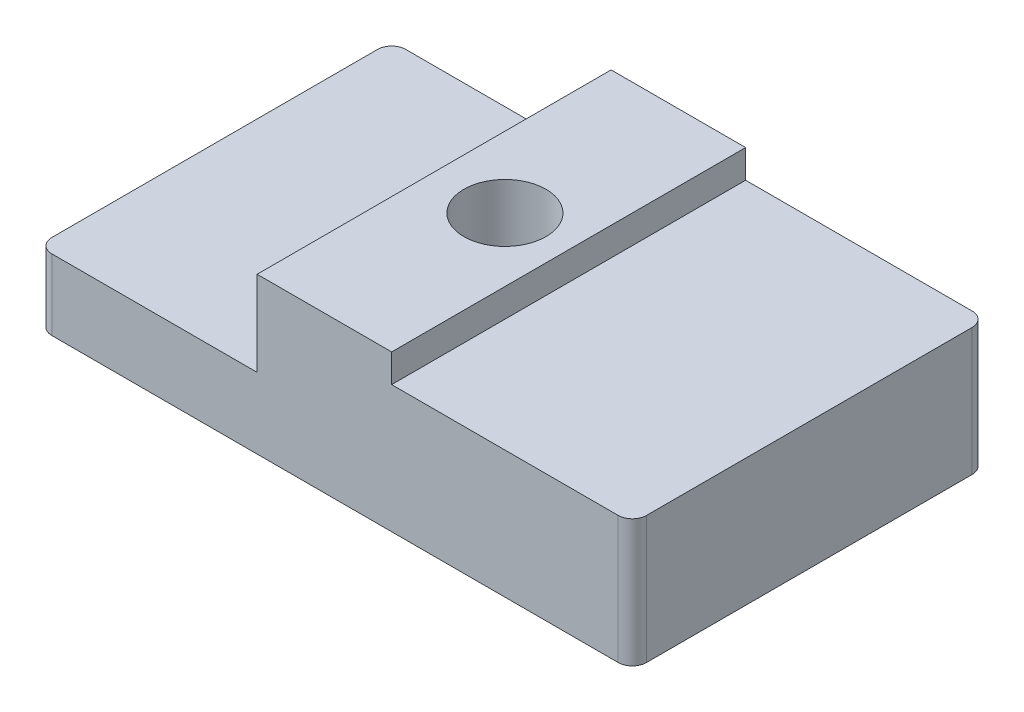
SolidWorks part; units mm, degrees
ref_plane "Front Plane" through (0, 0, 0) normal (0, 0, 1) x (1, 0, 0)
ref_plane "Top Plane" through (0, 0, 0) normal (0, 1, 0) x (1, 0, 0)
ref_plane "Right Plane" through (0, 0, 0) normal (1, 0, 0) x (0, 0, -1)
sketch "Sketch1" plane through (0, 0, 0) normal (0, 1, 0) x (1, 0, 0)
  line L1 (0, 0) -> (45, 0)
  line L2 (0, 0) -> (0, 25)
  line L3 (0, 25) -> (45, 25)
  line L4 (45, 0) -> (45, 25)
  dimension "D1" = 45
  dimension "D2" = 25
extrude "Boss-Extrude1" add sketch "Sketch1" along normal blind 5 contours L1 L4 L3 L2 region at (22.5, 0, -12.5)
sketch "Sketch5" plane through (0, 5, 0) normal (0, 1, 0) x (1, 0, 0)
  line L0 (0, 25) -> (45, 25) construction
  line L1 (18.5, 25) -> (45, 25)
  line L2 (18.5, 25) -> (18.5, 0)
  line L3 (18.5, 0) -> (45, 0)
  line L4 (45, 25) -> (45, 0)
  line L5 (45, 0) -> (45, 25) construction
  line L6 (0, 0) -> (45, 0) construction
  dimension "D1" = 26.5
extrude "Boss-Extrude3" add sketch "Sketch5" along normal blind 4
sketch "Sketch11" plane through (0, 9, 0) normal (0, 1, 0) x (1, 0, 0)
  line L0 (18.5, 25) -> (18.5, 0) construction
  line L1 (18.5, 25) -> (28, 25)
  line L2 (18.5, 25) -> (18.5, 0)
  line L3 (18.5, 0) -> (28, 0)
  line L4 (28, 25) -> (28, 0)
  line L5 (45, 25) -> (18.5, 25) construction
  line L6 (18.5, 0) -> (45, 0) construction
  dimension "D1" = 9.5
extrude "Boss-Extrude5" add sketch "Sketch11" along normal blind 2
sketch "Sketch12" plane through (0, 5, 0) normal (0, 1, 0) x (1, 0, 0)
  line L0 (0, 25) -> (18.5, 25) construction
  line L1 (0, 25) -> (3, 25)
  line L2 (0, 25) -> (0, 0)
  line L3 (0, 0) -> (3, 0)
  line L4 (3, 25) -> (3, 0)
  line L5 (0, 0) -> (0, 25) construction
  line L6 (0, 0) -> (18.5, 0) construction
  dimension "D1" = 3
extrude "Cut-Extrude2" cut sketch "Sketch12" against normal through all
sketch "Sketch13" plane through (0, 0, 0) normal (0, -1, 0) x (-1, 0, 0)
  line L0 (-23.5, 0) -> (-23.5, 25) construction
  line L1 (-3, 0) -> (-45, 0) construction
  line L2 (-3, 25) -> (-45, 25) construction
  line L3 (-45, 0) -> (-45, 25) construction
  point P8 (-23.5, 12.5)
  dimension "D1" = 21.5
hole_wizard "M5 Clearance Hole1" positions "Sketch14" profile "Sketch15" hole size "M5" standard "ISO" end condition through all
sketch "Sketch14" plane through (0, 0, 0) normal (0, -1, 0) x (-1, 0, 0)
  point P0 (-23.5, 12.5)
sketch "Sketch15" plane through (23.5, 0, -12.5) normal (1, 0, 0) x (0, 0, -1)
  line L0 (0, 0) -> (0, 11)
  line L1 (0, 11) -> (2.9, 11)
  line L2 (2.9, 11) -> (2.9, 0)
  line L5 (2.9, 0) -> (0, 0)
  line L11 (0, -6.35) -> (0, 107.95) construction
  dimension "Thru Hole Dia." = 5.8
  dimension "Thru Hole Depth" = 11
fillet "Fillet1" radius 1 4 edges at (45, 4.5, -25) (45, 4.5, 0) (3, 2.5, -25) (3, 2.5, 0)
